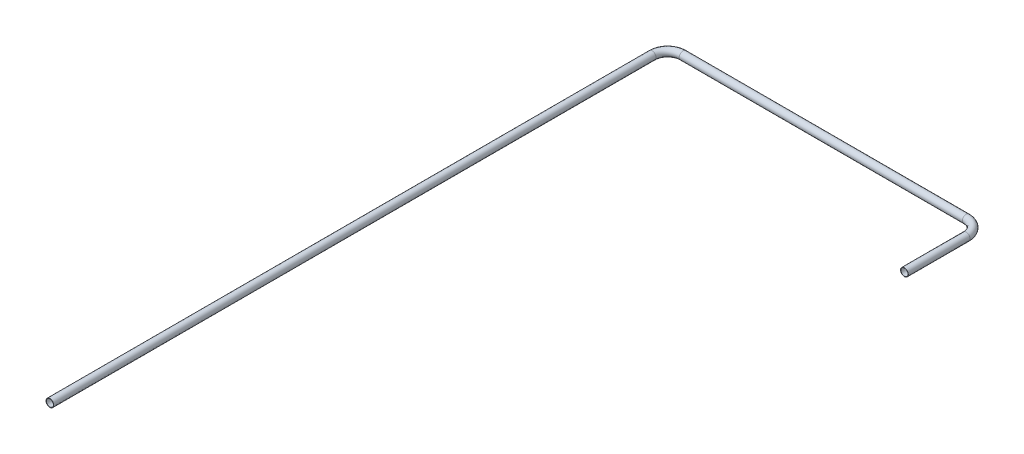
SolidWorks part; units mm, degrees
ref_plane "Front" through (0, 0, 0) normal (0, 0, 1) x (1, 0, 0)
ref_plane "Top" through (0, 0, 0) normal (0, 1, 0) x (1, 0, 0)
ref_plane "Right" through (0, 0, 0) normal (1, 0, 0) x (0, 0, -1)
sketch "Sketch13" plane through (0, 0, 0) normal (0, 1, 0) x (1, 0, 0)
  line L0 (-152.4, 0) -> (-2946.4, 0)
  line L1 (-3098.8, -152.4) -> (-3098.8, -6096)
  line L2 (0, -152.4) -> (0, -762)
  arc A0 (-3098.8, -152.4) -> (-2946.4, 0) centre (-2946.4, -152.4) cw
  arc A1 (0, -152.4) -> (-152.4, 0) centre (-152.4, -152.4) ccw
  point P7 (-3098.8, 0)
  point P10 (0, 0)
  dimension "D3" = 152.4
  dimension "D1" = 6096
  dimension "D2" = 762
  dimension "D4" = 2794
ref_plane "Plane1" through (0, 0, 762) normal (0, 0, 1) x (1, 0, 0)
sketch "Sketch14" plane through (0, 0, 762) normal (0, 0, 1) x (1, 0, 0)
  line L0 (0, 34.925) -> (0, 38.1) construction
  circle A0 centre (0, 0) radius 38.1
  circle A1 centre (0, 0) radius 34.925
  dimension "D1" = 76.2
  dimension "D2" = 3.175
sweep "Sweep1" add profiles "Sketch14" path "Sketch13"
sketch "Sketch15" plane through (0, 0, 0) normal (0, 1, 0) x (1, 0, 0)
  line L0 (0, -762) -> (0, -787.4)
  line L1 (-38.1, -762) -> (38.1, -762) construction
  line L2 (50.8, -838.2) -> (2501.9, -838.2)
  arc A0 (0, -787.4) -> (50.8, -838.2) centre (50.8, -787.4) ccw
  dimension "D1" = 50.8
  dimension "D2" = 25.4
  dimension "D3" = 2451.1
sketch "Sketch16" plane through (0, 0, 762) normal (0, 0, 1) x (1, 0, 0)
  circle A0 centre (0, 0) radius 34.925 construction
  circle A1 centre (0, 0) radius 38.1
  circle A2 centre (0, 0) radius 38.1
  circle A3 centre (0, 0) radius 34.925
  dimension "D1" = 0
sketch "Sketch17" plane through (0, 0, 0) normal (0, 1, 0) x (1, 0, 0)
  line L0 (0, -762) -> (0, -787.4)
  line L1 (-38.1, -762) -> (38.1, -762) construction
  line L2 (50.8, -838.2) -> (914.4, -838.2)
  line L3 (965.2, -889) -> (965.2, -939.8)
  line L4 (1016, -990.6) -> (1117.6, -990.6)
  line L5 (1168.4, -939.8) -> (1168.4, -889)
  line L6 (50.8, -838.2) -> (2501.9, -838.2) construction
  line L7 (1219.2, -838.2) -> (2501.9, -838.2)
  arc A0 (0, -787.4) -> (50.8, -838.2) centre (50.8, -787.4) ccw
  arc A1 (965.2, -889) -> (914.4, -838.2) centre (914.4, -889) ccw
  arc A2 (1016, -990.6) -> (965.2, -939.8) centre (1016, -939.8) cw
  arc A3 (1168.4, -939.8) -> (1117.6, -990.6) centre (1117.6, -939.8) cw
  arc A4 (1219.2, -838.2) -> (1168.4, -889) centre (1219.2, -889) ccw
  point P17 (965.2, -838.2)
  point P20 (965.2, -990.6)
  point P23 (1168.4, -990.6)
  point P26 (1168.4, -838.2)
  dimension "D3" = 50.8
  dimension "D6" = 50.8
  dimension "D7" = 50.8
  dimension "D8" = 50.8
  dimension "D9" = 50.8
  dimension "D1" = 914.4
  dimension "D2" = 25.4
  dimension "D4" = 152.4
  dimension "D5" = 203.2
sketch "Sketch18" plane through (0, 0, 762) normal (0, 0, 1) x (1, 0, 0)
  circle A2 centre (0, 0) radius 38.1
  circle A3 centre (0, 0) radius 34.925
sweep "Sweep3" [suppressed] add profiles "Sketch18" path "Sketch17"
